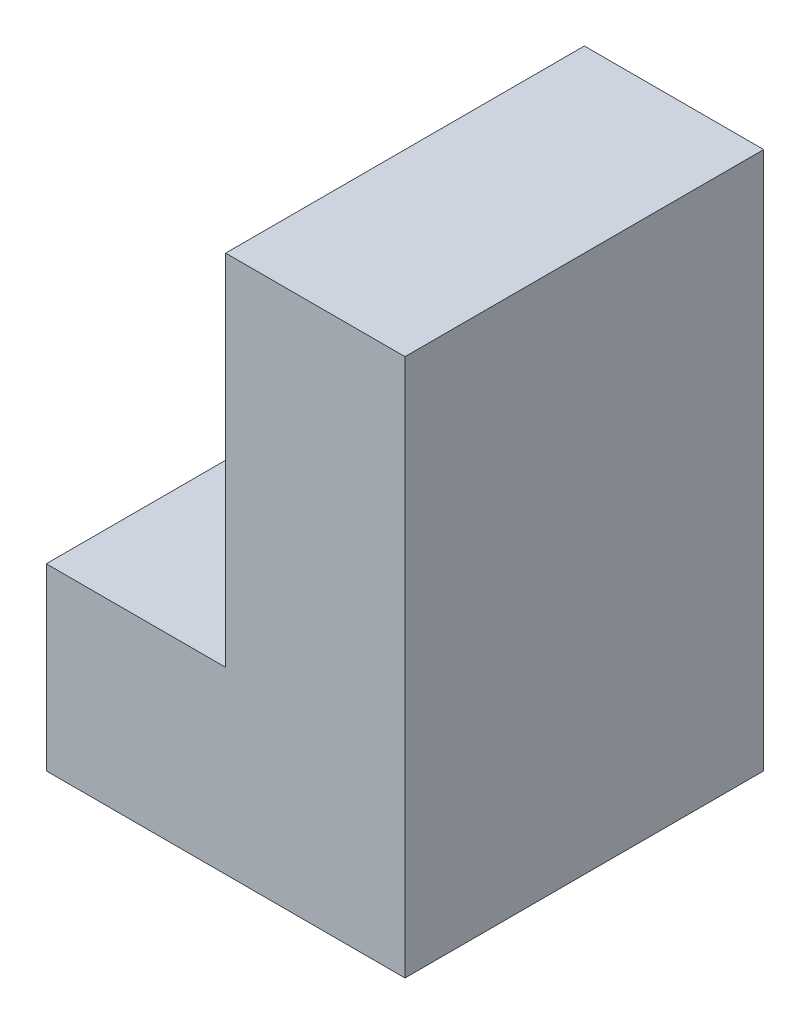
SolidWorks part; units mm, degrees
ref_plane "Plano frontal" through (0, 0, 0) normal (0, 0, 1) x (1, 0, 0)
ref_plane "Plano superior" through (0, 0, 0) normal (0, 1, 0) x (1, 0, 0)
ref_plane "Plano direito" through (0, 0, 0) normal (1, 0, 0) x (0, 0, -1)
sketch "Esboço1" plane through (0, 0, 0) normal (0, 0, 1) x (1, 0, 0)
  line L0 (0, 0) -> (0, -10)
  line L1 (0, -10) -> (20, -10)
  line L2 (20, -10) -> (20, 20)
  line L3 (20, 20) -> (10, 20)
  line L4 (10, 20) -> (10, 0)
  line L5 (10, 0) -> (0, 0)
  dimension "D1" = 20
  dimension "D2" = 30
  dimension "D3" = 10
  dimension "D4" = 10
extrude "Ressalto-extrusão1" add sketch "Esboço1" against normal blind 20
